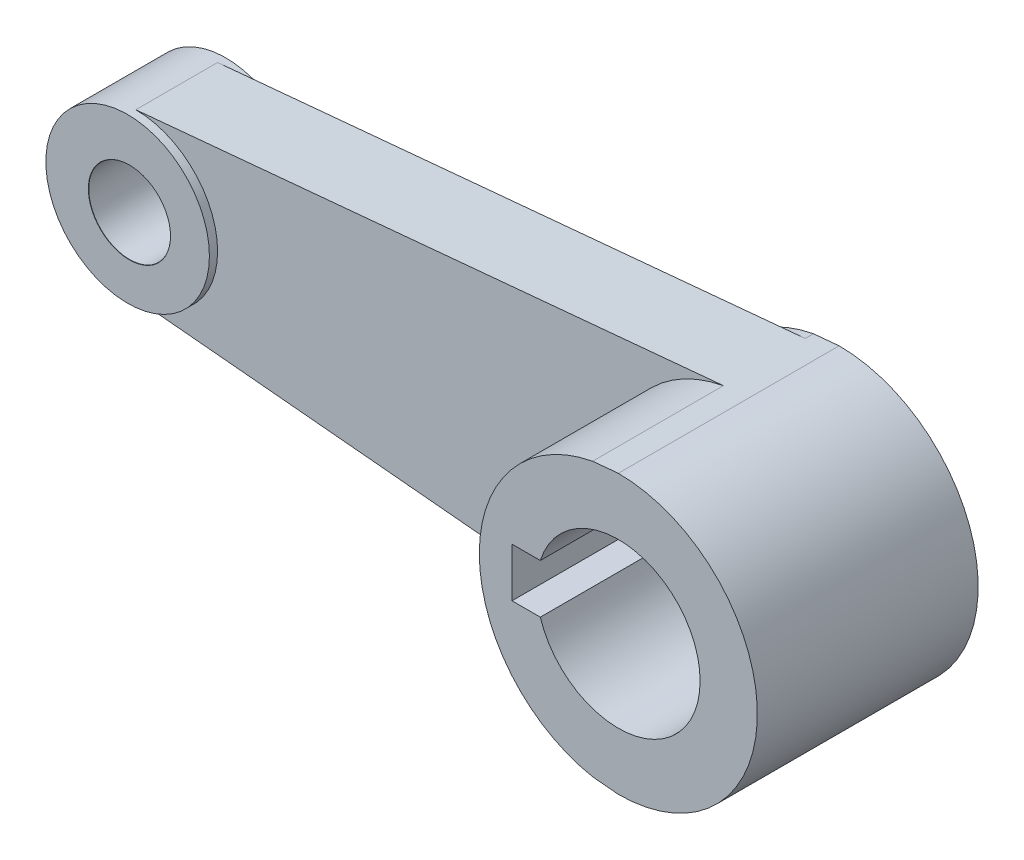
SolidWorks part; units mm, degrees
note: The reader was unsure of these and kept them because the rebuilt part matched: shared geometry of "Schizzo1<4>", "Schizzo1<5>".
ref_plane "Piano frontale" through (0, 0, 0) normal (0, 0, 1) x (1, 0, 0)
ref_plane "Piano superiore" through (0, 0, 0) normal (0, 1, 0) x (1, 0, 0)
ref_plane "Piano destro" through (0, 0, 0) normal (1, 0, 0) x (0, 0, -1)
sketch "Schizzo1" plane through (0, 0, 0) normal (0, 0, 1) x (1, 0, 0)
  line L0 (-9.5394, 3) -> (-13, 3)
  line L1 (-90.6238, 0) -> (38.3938, 0) construction
  line L2 (-13, 3) -> (-13, -3)
  line L4 (-9.5394, -3) -> (-13, -3)
  line L5 (-75, 22.5989) -> (-75, -13.6308) construction
  line L6 (0, 30.3373) -> (0, -19.3995) construction
  line L7 (0, 17) -> (-75, 10)
  line L8 (-75, -10) -> (0, -17)
  circle A0 centre (-75, 0) radius 10
  circle A1 centre (0, 0) radius 17
  arc A3 (-9.5394, -3) -> (-9.5394, 3) centre (0, 0) ccw
  point P13 (-13, 0)
  point P17 (0, 0)
  point P18 (-75, 0)
  point P19 (0, 0)
  dimension "D1" = 20
  dimension "D2" = 34
  dimension "D3" = 10
  dimension "D4" = 75
  dimension "D5" = 6
  dimension "D6" = 13
extrude "Estrusione-Estrusione1" add sketch "Schizzo1" along normal mid plane 10 contours A1 L7 A0 L8
extrude "Estrusione-Estrusione2" add sketch "Schizzo1<4>" along normal mid plane 12 contours A0
sketch "Schizzo1<4>" plane through (0, 0, 0) normal (0, 0, 1) x (1, 0, 0) same geometry as "Schizzo1"
extrude "Estrusione-Estrusione3" add sketch "Schizzo1<5>" along normal blind 27 from offset 6 contours L7 A1 L8 A3 L4 L2 L0 offset against normal yes
sketch "Schizzo1<5>" plane through (0, 0, 0) normal (0, 0, 1) x (1, 0, 0) same geometry as "Schizzo1"
hole_wizard "Foro Ø10.0 (10)-1" positions "Schizzo3D1" profile "Schizzo3" hole size "Ø10.0" standard "ISO"
sketch3d "Schizzo3D1"
  point P11 (-74.7794, -0.2657, 6)
  point P13 (-75, 0, 0)
  point P17 (-74.7794, -0.2657, 6)
sketch "Schizzo3" plane through (-74.7794, -0.2657, 6) normal (1, 0, 0) x (0, -1, 0)
  line L0 (0, 0) -> (0, 12)
  line L1 (0, 12) -> (5, 12)
  line L2 (5, 12) -> (5, 0.025)
  line L3 (5, 0.025) -> (5.025, 0)
  line L5 (5.025, 0) -> (0, 0)
  line L6 (-5, 0.025) -> (-5.025, 0) construction
  line L11 (0, -6.35) -> (0, 107.95) construction
  dimension "Thru Hole Dia." = 10
  dimension "Thru Hole Depth" = 12
  dimension "Near C'Sink Dia." = 10.05
  dimension "Near C'Sink Angle" = 90
